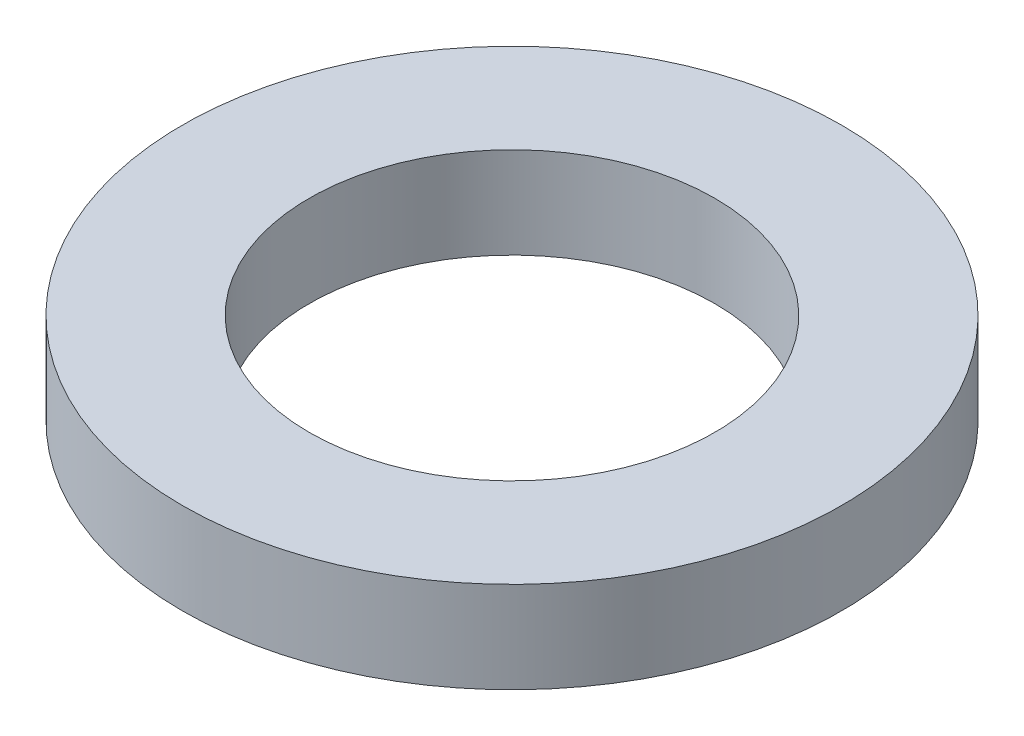
SolidWorks part; units mm, degrees
ref_plane "Front Plane" through (0, 0, 0) normal (0, 0, 1) x (1, 0, 0)
ref_plane "Top Plane" through (0, 0, 0) normal (0, 1, 0) x (1, 0, 0)
ref_plane "Right Plane" through (0, 0, 0) normal (1, 0, 0) x (0, 0, -1)
sketch "Sketch1" plane through (0, 0, 0) normal (0, 1, 0) x (1, 0, 0)
  circle A0 centre (0, 0) radius 32.5
  dimension "FLANGE_OD" = 65
extrude "Boss-Extrude1" add sketch "Sketch1" along normal blind 9
sketch "Sketch2" plane through (0, 0, 0) normal (0, 1, 0) x (1, 0, 0)
  circle A0 centre (0, 0) radius 20
  dimension "BORE_D" = 40
extrude "Cut-Extrude1" cut sketch "Sketch2" along normal through all
sketch "Sketch3" plane through (0, 9, 0) normal (0, 1, 0) x (1, 0, 0)
  circle A0 centre (0, 0) radius 12.7563 construction
  circle A1 centre (-12.7563, 0) radius 1.6721
  dimension "BOLT_D" = 3.3443
  dimension "BOLT_PCD" = 25.5125
extrude "Cut-Extrude2" cut sketch "Sketch3" against normal blind 6.6713 rebuild error yes
pattern_circular "CirPattern1" count 6 over 360 rebuild error yes
